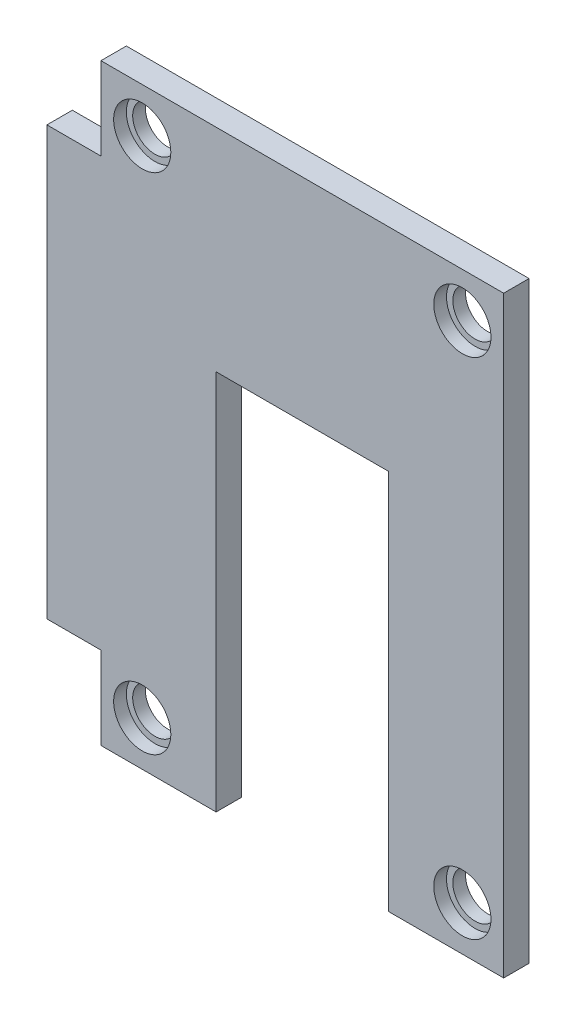
SolidWorks part; units mm, degrees
material "ABS"
ref_plane "Alzado" through (0, 0, 0) normal (0, 0, 1) x (1, 0, 0)
ref_plane "Planta" through (0, 0, 0) normal (0, 1, 0) x (1, 0, 0)
ref_plane "Vista lateral" through (0, 0, 0) normal (1, 0, 0) x (0, 0, -1)
sketch "Croquis1" plane through (0, 0, 0) normal (0, 0, 1) x (1, 0, 0)
  line L0 (0, 93.345) -> (64.3868, 93.345)
  line L1 (0, 93.345) -> (0, 0)
  line L2 (0, 0) -> (64.3868, 0)
  line L3 (64.3868, 93.345) -> (64.3868, 0)
  dimension "D1" = 64.3868
  dimension "D2" = 93.345
extrude "Saliente-Extruir1" add sketch "Croquis1" along normal blind 4
sketch "Croquis2" plane through (0, 0, 4) normal (0, 0, 1) x (1, 0, 0)
  line L5 (0, 0) -> (64.3868, 0) construction
  line L6 (18.63, 0) -> (45.7568, 0)
  line L7 (18.63, 0) -> (18.63, 60)
  line L8 (18.63, 60) -> (45.7568, 60)
  line L9 (45.7568, 0) -> (45.7568, 60)
  line L10 (64.3868, 0) -> (64.3868, 93.345) construction
  line L11 (0, 93.345) -> (0, 0) construction
  dimension "D1" = 18.63
  dimension "D2" = 18.63
  dimension "D3" = 60
extrude "Cortar-Extruir1" cut sketch "Croquis2" against normal through all
sketch "Croquis5" plane through (0, 0, 4) normal (0, 0, 1) x (1, 0, 0)
  line L0 (64.3868, 0) -> (64.3868, 93.345) construction
  line L1 (64.3868, 93.345) -> (0, 93.345) construction
  line L2 (0, 93.345) -> (0, 0) construction
  line L3 (45.7568, 0) -> (64.3868, 0) construction
  circle A0 centre (57.3868, 86.345) radius 4.5
  circle A1 centre (7, 86.345) radius 4.5
  circle A2 centre (57.3868, 7) radius 4.5
  circle A3 centre (7, 7) radius 4.5
  dimension "D5" = 9
  dimension "D1" = 7
  dimension "D2" = 7
  dimension "D3" = 7
  dimension "D4" = 7
  dimension "D6" = 7
extrude "Cortar-Extruir3" cut sketch "Croquis5" against normal blind 2
sketch "Croquis6" plane through (0, 0, 2) normal (0, 0, 1) x (1, 0, 0)
  circle A0 centre (7, 86.345) radius 3.5
  circle A1 centre (57.3868, 86.345) radius 3.5
  circle A2 centre (57.3868, 7) radius 3.5
  circle A3 centre (7, 7) radius 3.5
  dimension "D1" = 7
extrude "Cortar-Extruir4" cut sketch "Croquis6" against normal through all
sketch "Croquis7" plane through (0, 0, 0) normal (0, 0, -1) x (-1, 0, 0)
  line L0 (0, 13) -> (0, 80.345)
  line L3 (0, 13) -> (8, 13)
  line L4 (8, 80.345) -> (8, 13)
  line L5 (0, 93.345) -> (0, 0) construction
  line L6 (0, 80.345) -> (8, 80.345)
  line L7 (-64.3868, 93.345) -> (0, 93.345) construction
  dimension "D1" = 8
  dimension "D2" = 13
  dimension "D3" = 13
extrude "Saliente-Extruir4" add sketch "Croquis7" against normal through all
sketch "Croquis8" plane through (0, 0, 0) normal (0, 0, -1) x (-1, 0, 0)
  line L0 (-18.63, 60) -> (-18.63, 0) construction
  line L1 (8, 80.345) -> (-18.63, 80.345)
  line L2 (8, 80.345) -> (8, 13)
  line L3 (8, 13) -> (-18.63, 13)
  line L4 (-18.63, 80.345) -> (-18.63, 13)
extrude "Saliente-Extruir5" add sketch "Croquis8" against normal blind 2
sketch "Croquis9" plane through (0, 0, 0) normal (0, 0, -1) x (-1, 0, 0)
  line L0 (-64.3868, 93.345) -> (0, 93.345) construction
  line L1 (-63.8868, 93.345) -> (-0.5, 93.345) construction
  line L2 (-63.8868, 93.345) -> (-63.8868, 0)
  line L3 (-63.8868, 0) -> (-0.5, 0) construction
  line L4 (-0.5, 93.345) -> (-0.5, 0) construction
  line L5 (0, 0) -> (-18.63, 0) construction
  line L6 (0, 93.345) -> (0, 80.345) construction
  line L7 (-64.3868, 0) -> (-64.3868, 93.345) construction
  line L8 (-0.5, 93.345) -> (0, 93.345)
  line L9 (0, 93.345) -> (0, 80.345)
  line L10 (0, 80.345) -> (-0.5, 80.345)
  line L11 (-0.5, 0) -> (0, 0)
  line L12 (0, 0) -> (0, 13)
  line L13 (0, 13) -> (-0.5, 13)
  line L14 (8, 13) -> (0, 13) construction
  line L15 (-63.8868, 93.345) -> (-64.3868, 93.345)
  line L16 (-64.3868, 93.345) -> (-64.3868, 0)
  line L17 (-64.3868, 0) -> (-63.8868, 0)
  line L18 (-0.5, 13) -> (-0.5, 0)
  line L19 (-0.5, 80.345) -> (-0.5, 93.345)
  dimension "D1" = 0.5
  dimension "D2" = 0.5
extrude "Cortar-Extruir5" cut sketch "Croquis9" against normal blind 13
sketch "Croquis10" plane through (0, 0, 0) normal (0, 0, -1) x (-1, 0, 0)
  line L0 (8, 80.345) -> (-0.5, 80.345) construction
  line L1 (2, 56.345) -> (7, 56.345)
  line L2 (2, 56.345) -> (2, 36.345)
  line L3 (2, 36.345) -> (7, 36.345)
  line L4 (7, 56.345) -> (7, 36.345)
  line L5 (8, 13) -> (8, 80.345) construction
  dimension "D1" = 24
  dimension "D2" = 20
  dimension "D3" = 1
  dimension "D4" = 5
extrude "Saliente-Extruir6" add sketch "Croquis10" along normal blind 25
fillet "Redondeo1" radius 1 1 edges at (-7, 46.345, 0)
fillet "Redondeo2" radius 5 2 edges at (-5, 56.345, 0) (-5, 36.345, 0)
sketch "Croquis11" plane through (-7, 0, 0) normal (-1, 0, 0) x (0, 0, 1)
  line L0 (-25, 56.345) -> (-5, 56.345) construction
  line L1 (-22, 56.345) -> (0, 56.345) construction
  line L2 (-22, 56.345) -> (-22, 36.345) construction
  line L3 (-22, 36.345) -> (0, 36.345) construction
  line L4 (0, 56.345) -> (0, 36.345) construction
  line L5 (0, 31.345) -> (0, 61.345) construction
  line L6 (-25, 36.345) -> (-5, 36.345) construction
  circle A0 centre (-19.75, 46.345) radius 1.5
  circle A1 centre (-2.25, 46.345) radius 1.5
  point P16 (-22, 46.345)
  dimension "D4" = 3
  dimension "D5" = 3
  dimension "D1" = 22
  dimension "D2" = 17.5
  dimension "D3" = 2.25
extrude "Cortar-Extruir6" cut sketch "Croquis11" against normal through all both and the other way through all
